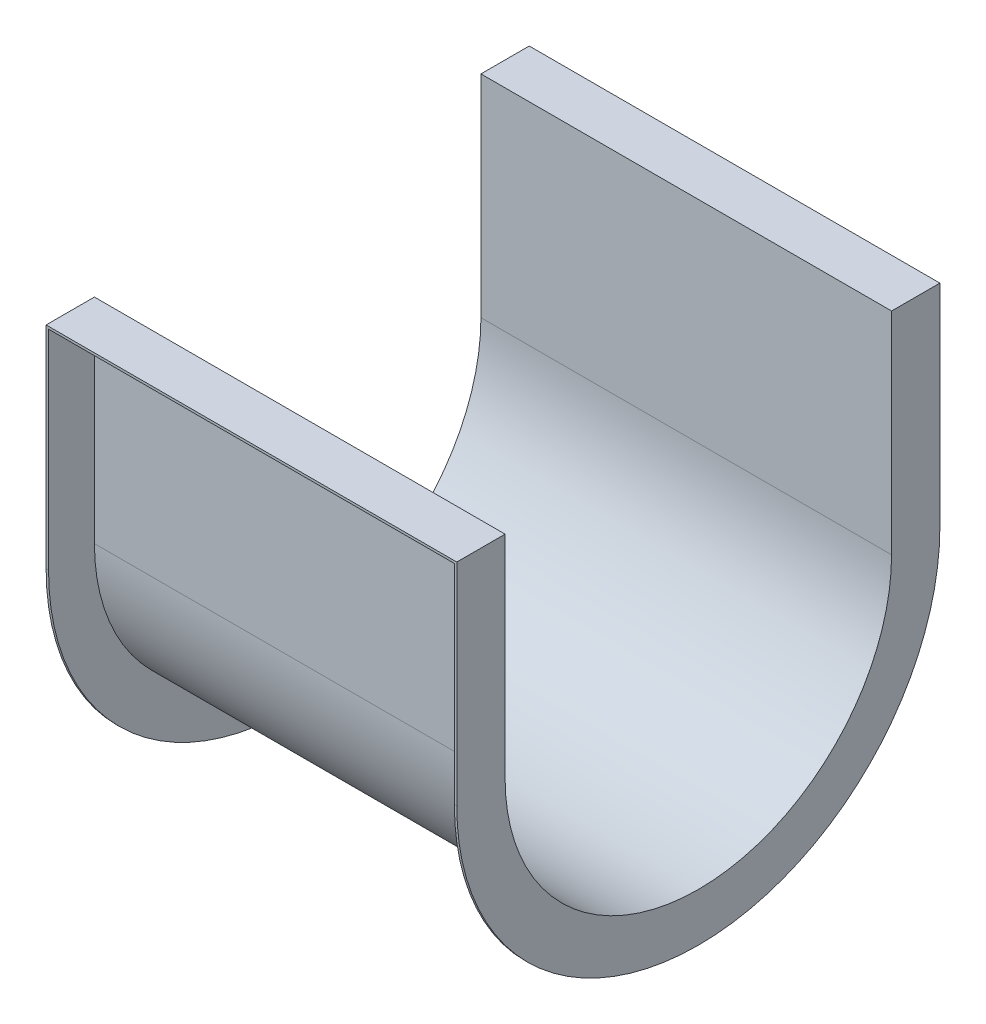
SolidWorks part; units mm, degrees
ref_plane "Front" through (0, 0, 0) normal (0, 0, 1) x (1, 0, 0)
ref_plane "Top" through (0, 0, 0) normal (0, 1, 0) x (1, 0, 0)
ref_plane "Right" through (0, 0, 0) normal (1, 0, 0) x (0, 0, -1)
sketch "Croquis1" plane through (0, 0, 0) normal (1, 0, 0) x (0, 0, -1)
  line L0 (80, 0) -> (100, 0)
  line L1 (100, 0) -> (100, -83.7)
  line L2 (33.9999, -183.7) -> (0, -183.7) construction
  line L3 (0, 0) -> (0, -183.7) construction
  line L8 (-33.9999, -183.7) -> (0, -183.7) construction
  line L9 (-100, 0) -> (-100, -83.7)
  line L10 (-80, 0) -> (-100, 0)
  line L12 (-80, 0) -> (-80, -83.7)
  line L13 (80, 0) -> (80, -83.7)
  line L15 (-80, -20) -> (-80, -83.7) construction
  line L16 (80, -20) -> (80, -83.7) construction
  line L17 (0, 0) -> (-100, 0) construction
  line L18 (0, -20) -> (-80, -20) construction
  line L19 (0, 0) -> (100, 0) construction
  line L20 (0, -20) -> (80, -20) construction
  arc A0 (0, -183.7) -> (100, -83.7) centre (0, -83.7) ccw
  arc A1 (0, -183.7) -> (-100, -83.7) centre (0, -83.7) cw
  arc A2 (0, -163.7) -> (-80, -83.7) centre (0, -83.7) cw
  arc A3 (0, -163.7) -> (80, -83.7) centre (0, -83.7) ccw
  dimension "D3" = 200
  dimension "D4" = 20
  dimension "D1" = 100
  dimension "D2" = 183.7
extrude "Saliente-Extruir1" add sketch "Croquis1" along normal blind 170
sketch "Croquis2" plane through (0, 0, 0) normal (0, 1, 0) x (1, 0, 0)
  line L1 (0, 100) -> (170, 100)
  line L2 (0, 100) -> (0, 80)
  line L3 (0, 80) -> (170, 80)
  line L4 (170, 100) -> (170, 80)
  line L5 (0, 100) -> (170, 80) construction
  line L6 (0, 80) -> (170, 100) construction
  line L7 (170, -80) -> (0, -80)
  line L8 (170, -80) -> (170, -100)
  line L9 (170, -100) -> (0, -100)
  line L10 (0, -80) -> (0, -100)
  line L11 (170, -80) -> (0, -100) construction
  line L12 (170, -100) -> (0, -80) construction
  point P4 (85, 90)
  point P11 (85, -90)
extrude "Saliente-Extruir2" add sketch "Croquis2" along normal blind 3.7
shell "Vaciado1" thickness 1 removed face at (85, -40, -100) removed face at (85, -133.7, 0) removed face at (85, -40, 100)
